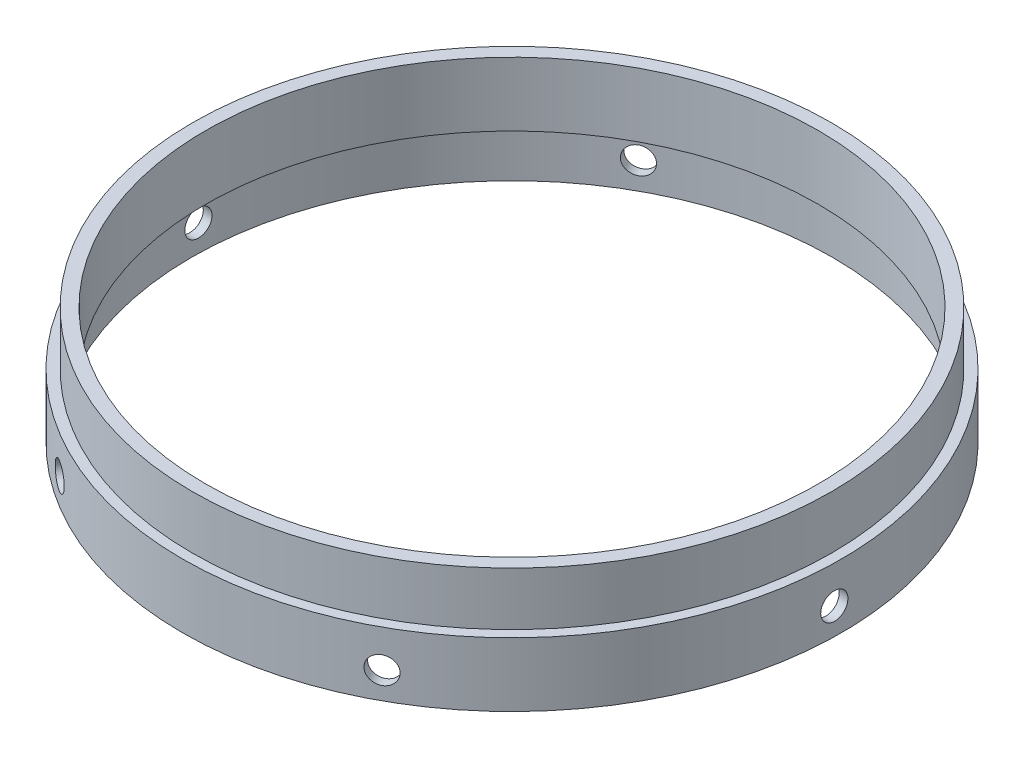
SolidWorks part; units mm, degrees
material "6061-T6 (SS)"
ref_plane "Front Plane" through (0, 0, 0) normal (0, 0, 1) x (1, 0, 0)
ref_plane "Top Plane" through (0, 0, 0) normal (0, 1, 0) x (1, 0, 0)
ref_plane "Right Plane" through (0, 0, 0) normal (1, 0, 0) x (0, 0, -1)
ref_axis "Axis1" through (0, -55, 0) along (0, 1, 0)
sketch "Sketch1" plane through (0, 0, 0) normal (0, 0, 1) x (1, 0, 0)
  line L0 (78.5876, 0) -> (78.5876, 15.24)
  line L1 (78.5876, 15.24) -> (76.2, 15.24)
  line L2 (76.2, 15.24) -> (76.2, 27.94)
  line L3 (76.2, 27.94) -> (73.025, 27.94)
  line L4 (73.025, 27.94) -> (73.025, 12.7)
  line L5 (73.025, 12.7) -> (76.454, 12.7)
  line L6 (76.454, 12.7) -> (76.454, 0)
  line L7 (76.454, 0) -> (78.5876, 0)
  line L8 (0, -55) -> (0, 55) construction
  line L9 (55, 0) -> (-55, 0) construction
  dimension "D1" = 78.5876
  dimension "D2" = 76.454
  dimension "D3" = 76.2
  dimension "D4" = 2.54
  dimension "D5" = 73.025
  dimension "D6" = 12.7
  dimension "D7" = 12.7
revolve "Revolve1" add sketch "Sketch1" angle 360 about axis through (0, -55, 0) along (0, 1, 0)
hole_wizard "1/4 (0.25) Diameter Hole1" positions "3DSketch1" profile "Sketch2" hole size "1/4" standard "ANSI Inch" end condition up to next
sketch3d "3DSketch1"
  point P0 (37.8571, 6.35, 68.8684)
  dimension "D1" = 6.35
sketch "Sketch2" plane through (37.8571, 6.35, 68.8684) normal (0, 1, 0) x (0.8763, 0, -0.4817)
  line L0 (0, 0) -> (0, 183.5913)
  line L1 (0, 183.5913) -> (3.175, 183.5913)
  line L2 (3.175, 183.5913) -> (3.175, 0)
  line L5 (3.175, 0) -> (0, 0)
  line L11 (0, -6.35) -> (0, 107.95) construction
  dimension "Thru Hole Dia." = 6.35
  dimension "Thru Hole Depth" = 183.5913
pattern_circular "CirPattern1" count 6 over 360 about axis through (0, -55, 0) along (0, 1, 0) of "1/4 (0.25) Diameter Hole1"
